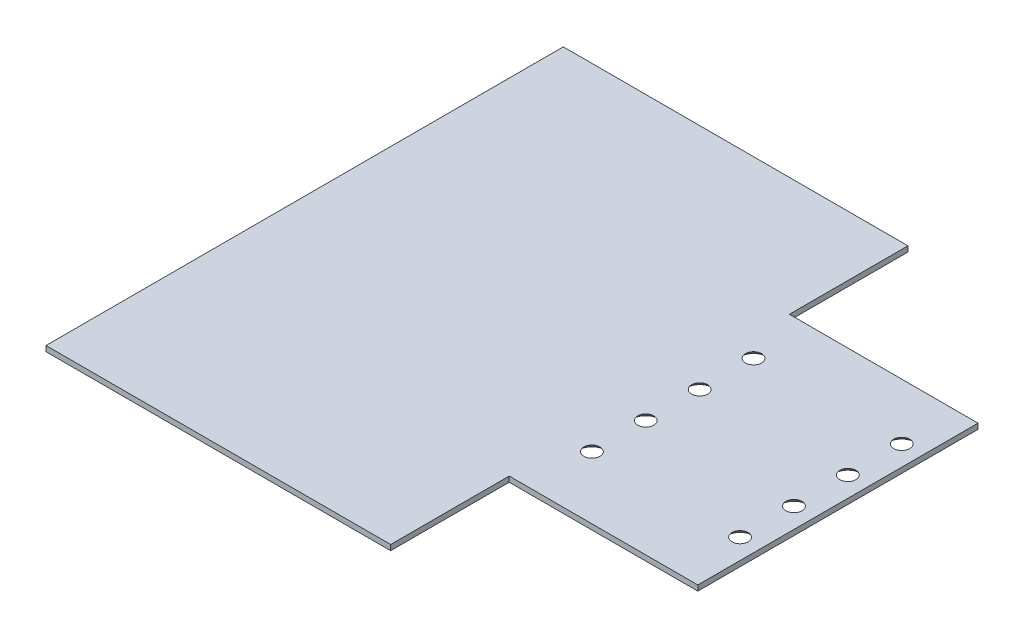
SolidWorks part; units mm, degrees
ref_plane "Спереди" through (0, 0, 0) normal (0, 0, 1) x (1, 0, 0)
ref_plane "Сверху" through (0, 0, 0) normal (0, 1, 0) x (1, 0, 0)
ref_plane "Справа" through (0, 0, 0) normal (1, 0, 0) x (0, 0, -1)
sketch "Эскиз1" plane through (0, 0, 0) normal (0, 1, 0) x (1, 0, 0)
  line L0 (15, -26) -> (15, -48)
  line L4 (15, 48) -> (15, 26)
  line L5 (50, 26) -> (15, 26)
  line L6 (50, 26) -> (50, -26)
  line L7 (50, -26) -> (15, -26)
  line L8 (-48.9591, 48) -> (15, 48)
  line L9 (-48.9591, 48) -> (-48.9591, -48)
  line L10 (-50, 0) -> (50, 0) construction
  line L11 (-48.9591, -48) -> (15, -48)
extrude "Бобышка-Вытянуть1" add sketch "Эскиз1" along normal blind 1
sketch "Эскиз2" plane through (0, 1, 0) normal (0, 1, 0) x (1, 0, 0)
  circle A0 centre (46.25, -14.4) radius 1.5
  circle A1 centre (18.75, -14.4) radius 1.5
  circle A2 centre (18.75, -4.4) radius 1.5
  circle A3 centre (46.25, -4.4) radius 1.5
  circle A4 centre (18.75, 5.6) radius 1.5
  circle A5 centre (46.25, 5.6) radius 1.5
  circle A6 centre (18.75, 15.6) radius 1.5
  circle A7 centre (46.25, 15.6) radius 1.5
  dimension "D1" = 4
extrude "Вырез-Вытянуть1" cut sketch "Эскиз2" against normal blind 10
chamfer "Фаска1" distance 1 angle 45 8 edges at (18.75, 0, -17.1) (18.75, 0, -7.1) (18.75, 0, 2.9) (18.75, 0, 12.9) (46.25, 0, -17.1) (46.25, 0, -7.1) (46.25, 0, 2.9) (46.25, 0, 12.9)
